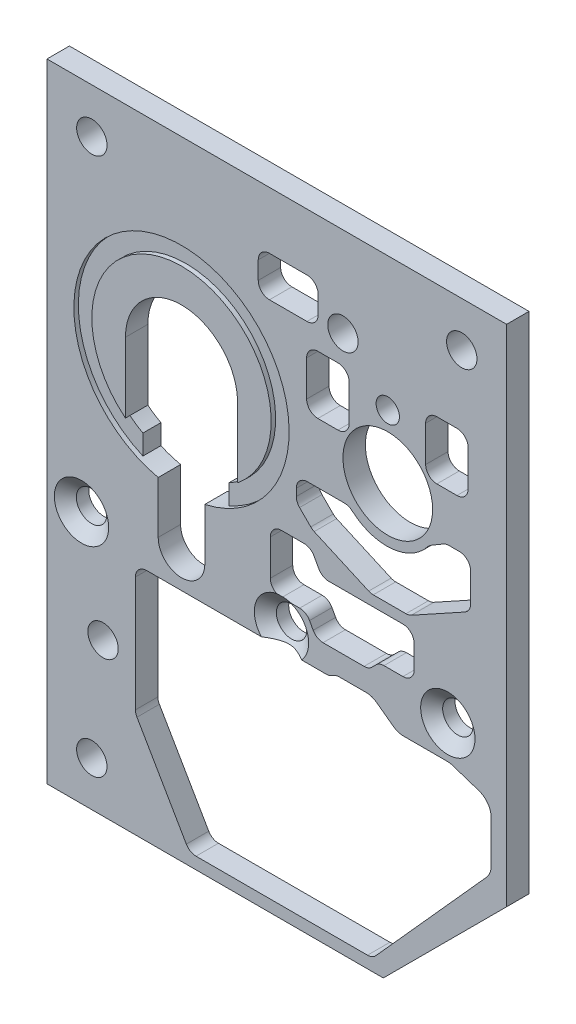
SolidWorks part; units mm, degrees
material "Acrylic (Medium-high impact)"
ref_plane "Front Plane" through (0, 0, 0) normal (0, 0, 1) x (1, 0, 0)
ref_plane "Top Plane" through (0, 0, 0) normal (0, 1, 0) x (1, 0, 0)
ref_plane "Right Plane" through (0, 0, 0) normal (1, 0, 0) x (0, 0, -1)
sketch "Sketch1" plane through (0, 0, 0) normal (0, 0, 1) x (1, 0, 0)
  line L5 (-65.0875, 0) -> (-65.0875, -88.9)
  line L6 (-65.0875, -88.9) -> (-17.4625, -88.9)
  line L7 (-17.4625, -88.9) -> (0, -71.4375)
  line L8 (0, -71.4375) -> (0, 0)
  line L9 (0, 0) -> (-65.0875, 0)
  line L10 (-65.0875, 0) -> (-65.0875, -88.9)
  line L11 (-65.0875, -88.9) -> (-17.4625, -88.9)
  line L12 (-17.4625, -88.9) -> (0, -71.4375)
  line L13 (0, -71.4375) -> (0, 0)
  line L14 (0, 0) -> (-65.0875, 0)
  dimension "D1" = 0
extrude "Boss-Extrude1" add sketch "Sketch1" against normal blind 3.175
hole_wizard "#6 Clearance Hole1" positions "Sketch3" profile "Sketch2" hole size "#6" standard "ANSI Inch" end condition through all
sketch "Sketch3" plane through (0, 0, 0) normal (0, 0, 1) x (1, 0, 0)
  point P0 (-58.7375, -6.35)
  point P3 (-6.35, -6.35)
  point P6 (-23.1775, -12.7)
  point P9 (-57.15, -67.31)
  point P12 (-58.7375, -82.55)
sketch "Sketch2" plane through (-58.7375, -6.35, 0) normal (1, 0, 0) x (0, -1, 0)
  line L0 (0, 0) -> (0, 3.175)
  line L1 (0, 3.175) -> (2.1526, 3.175)
  line L2 (2.1526, 3.175) -> (2.1526, 0)
  line L5 (2.1526, 0) -> (0, 0)
  line L11 (0, -6.35) -> (0, 107.95) construction
  dimension "Thru Hole Dia." = 4.3053
  dimension "Thru Hole Depth" = 3.175
sketch "Sketch4" plane through (0, 0, 0) normal (0, 0, 1) x (1, 0, 0)
  line L0 (-49.3395, -50.8) -> (-49.3395, -43.453) construction
  line L1 (-42.7355, -43.453) -> (-42.7355, -50.8) construction
  line L2 (-49.3395, -50.8) -> (-49.3395, -43.453)
  line L3 (-42.7355, -43.453) -> (-42.7355, -50.8)
  arc A0 (-42.7355, -43.453) -> (-49.3395, -43.453) centre (-46.0375, -28.575) ccw construction
  arc A1 (-49.3395, -50.8) -> (-42.7355, -50.8) centre (-46.0375, -50.8) ccw construction
  arc A2 (-42.7355, -43.453) -> (-49.3395, -43.453) centre (-46.0375, -28.575) ccw
  arc A3 (-49.3395, -50.8) -> (-42.7355, -50.8) centre (-46.0375, -50.8) ccw
extrude "Cut-Extrude1" cut sketch "Sketch4" against normal through all
sketch "Sketch5" plane through (0, 0, 0) normal (0, 0, 1) x (1, 0, 0)
  circle A0 centre (-16.8275, -27.94) radius 6.35
  circle A1 centre (-16.8275, -18.9484) radius 1.651
  dimension "D1" = 12.7
  dimension "D2" = 3.302
  dimension "D3" = 8.9916
extrude "Cut-Extrude2" cut sketch "Sketch5" against normal through all
hole_wizard "1/4 Clearance Hole1" positions "Sketch7" profile "Sketch6" hole size "1/4" standard "ANSI Inch" end condition through all
sketch "Sketch7" plane through (0, 0, 0) normal (0, 0, 1) x (1, 0, 0)
  point P0 (-9.2075, -65.0875)
sketch "Sketch6" plane through (-9.2075, -65.0875, 0) normal (1, 0, 0) x (0, -1, 0)
  line L0 (0, 0) -> (0, 3.175)
  line L1 (0, 3.175) -> (3.5712, 3.175)
  line L2 (3.5712, 3.175) -> (3.5712, 0)
  line L5 (3.5712, 0) -> (0, 0)
  line L11 (0, -6.35) -> (0, 107.95) construction
  dimension "Thru Hole Dia." = 7.1425
  dimension "Thru Hole Depth" = 3.175
sketch "Sketch8" plane through (0, 0, -3.175) normal (0, 0, -1) x (-1, 0, 0)
  line L0 (52.1335, -39.7163) -> (52.1335, -42.5427) construction
  line L1 (53.975, -28.575) -> (53.975, -38.4889) construction
  line L2 (38.1, -38.4889) -> (38.1, -28.575) construction
  line L3 (39.9415, -42.5427) -> (39.9415, -39.7163) construction
  line L4 (52.1335, -39.7163) -> (52.1335, -42.5427)
  line L5 (53.975, -28.575) -> (53.975, -38.4889)
  line L6 (38.1, -38.4889) -> (38.1, -28.575)
  line L7 (39.9415, -42.5427) -> (39.9415, -39.7163)
  arc A0 (52.1335, -39.7163) -> (53.975, -38.4889) centre (46.0375, -28.575) ccw construction
  arc A1 (53.975, -28.575) -> (38.1, -28.575) centre (46.0375, -28.575) ccw construction
  arc A2 (38.1, -38.4889) -> (39.9415, -39.7163) centre (46.0375, -28.575) ccw construction
  arc A3 (49.3395, -43.453) -> (42.7355, -43.453) centre (46.0375, -28.575) ccw construction
  arc A4 (52.1335, -39.7163) -> (53.975, -38.4889) centre (46.0375, -28.575) ccw
  arc A5 (53.975, -28.575) -> (38.1, -28.575) centre (46.0375, -28.575) ccw
  arc A6 (38.1, -38.4889) -> (39.9415, -39.7163) centre (46.0375, -28.575) ccw
  arc A7 (52.1335, -42.5427) -> (39.9415, -42.5427) centre (46.0375, -28.575) ccw
extrude "Boss-Extrude2" add sketch "Sketch8" against normal through all
sketch "Sketch9" plane through (0, 0, 0) normal (0, 0, 1) x (1, 0, 0)
  line L0 (-52.1335, -39.7163) -> (-52.1335, -42.5427) construction
  line L1 (-39.9415, -42.5427) -> (-39.9415, -39.7163) construction
  line L2 (-52.1335, -39.7163) -> (-52.1335, -42.5427)
  line L3 (-39.9415, -42.5427) -> (-39.9415, -39.7163)
  arc A0 (-42.7355, -43.453) -> (-49.3395, -43.453) centre (-46.0375, -28.575) ccw construction
  arc A1 (-53.975, -38.4889) -> (-52.1335, -39.7163) centre (-46.0375, -28.575) ccw construction
  arc A2 (-38.1, -38.4889) -> (-53.975, -38.4889) centre (-46.0375, -28.575) ccw construction
  arc A3 (-39.9415, -39.7163) -> (-38.1, -38.4889) centre (-46.0375, -28.575) ccw construction
  arc A4 (-39.9415, -42.5427) -> (-52.1335, -42.5427) centre (-46.0375, -28.575) ccw
  arc A5 (-53.975, -38.4889) -> (-52.1335, -39.7163) centre (-46.0375, -28.575) ccw
  arc A6 (-38.1, -38.4889) -> (-53.975, -38.4889) centre (-46.0375, -28.575) ccw
  arc A7 (-39.9415, -39.7163) -> (-38.1, -38.4889) centre (-46.0375, -28.575) ccw
extrude "Cut-Extrude3" cut sketch "Sketch9" against normal blind 0.635
hole_wizard "CSK for #6 Flat Head Machine Screw (100)1" positions "Sketch11" profile "Sketch10" countersink size "#6" standard "ANSI Inch" end condition through all
sketch "Sketch11" plane through (0, 0, 0) normal (0, 0, 1) x (1, 0, 0)
  point P1 (-31.877, -53.0919)
  point P5 (-60.198, -53.0919)
  point P8 (-8.321, -53.0919)
sketch "Sketch10" plane through (-31.877, -53.0919, 0) normal (1, 0, 0) x (0, -1, 0)
  line L0 (0, 0) -> (0, 3.175)
  line L1 (0, 3.175) -> (2.1526, 3.175)
  line L2 (2.1526, 3.175) -> (2.1526, 1.4209)
  line L3 (2.1526, 1.4209) -> (3.846, 0)
  line L5 (3.846, 0) -> (0, 0)
  line L6 (-2.1526, 1.4209) -> (-3.846, 0) construction
  line L11 (0, -6.35) -> (0, 107.95) construction
  dimension "Thru Hole Dia." = 4.3053
  dimension "Thru Hole Depth" = 3.175
  dimension "Near C'Sink Dia." = 7.692
  dimension "Near C'Sink Angle" = 100
sketch "Sketch13" plane through (0, 0, 0) normal (0, 0, 1) x (1, 0, 0)
  line L0 (-33.5834, -8.0877) -> (-28.2715, -8.0877)
  line L1 (-26.684, -9.6752) -> (-26.684, -12.1963)
  line L2 (-28.2715, -13.7838) -> (-33.5834, -13.7838)
  line L3 (-35.1709, -9.6752) -> (-35.1709, -12.1963)
  line L4 (-9.8743, -16.2715) -> (-7.0294, -16.2715)
  line L5 (-5.4419, -17.859) -> (-5.4419, -22.9231)
  line L6 (-7.0294, -24.5106) -> (-9.8743, -24.5106)
  line L7 (-11.4618, -22.9231) -> (-11.4618, -17.859)
  line L8 (-26.728, -16.6728) -> (-23.8831, -16.6728)
  line L9 (-22.2956, -18.2603) -> (-22.2956, -23.3243)
  line L10 (-23.8831, -24.9118) -> (-26.728, -24.9118)
  line L11 (-28.3155, -23.3243) -> (-28.3155, -18.2603)
  line L17 (-13.0908, -45.6924) -> (-13.0908, -48.9531)
  line L23 (-33.4611, -47.8684) -> (-33.4611, -42.8044)
  line L24 (-29.3162, -37.1302) -> (-27.7292, -38.7172)
  line L25 (-27.2516, -39.0452) -> (-19.5276, -42.4798)
  line L26 (-18.8826, -42.6167) -> (-14.2496, -42.6167)
  line L27 (-13.4825, -42.4191) -> (-5.915, -38.243)
  line L28 (-5.0945, -36.8531) -> (-5.0945, -32.7951)
  line L29 (-6.682, -31.2076) -> (-8.167, -31.2076)
  line L32 (-22.9356, -33.4058) -> (-28.1937, -33.4058)
  line L33 (-29.7812, -34.9933) -> (-29.7812, -36.0077)
  line L34 (-50.973, -55.6802) -> (-25.5623, -55.6802)
  line L40 (-19.6965, -87.2192) -> (-43.9811, -87.2192)
  line L41 (-45.3548, -86.4273) -> (-52.3467, -74.3556)
  line L42 (-52.5605, -73.56) -> (-52.5605, -57.2677)
  line L43 (-14.6783, -44.1049) -> (-25.206, -44.1049)
  line L44 (-26.5981, -43.2804) -> (-27.2773, -42.0413)
  line L45 (-28.6694, -41.2169) -> (-31.8736, -41.2169)
  line L48 (-25.9975, -52.0435) -> (-20.1851, -52.0435)
  line L49 (-19.0626, -51.5785) -> (-18.4896, -51.0056)
  line L50 (-17.3671, -50.5406) -> (-14.6783, -50.5406)
  line L51 (-27.3896, -51.219) -> (-27.9041, -50.2804)
  line L52 (-29.2962, -49.4559) -> (-31.8736, -49.4559)
  line L54 (-24.662, -55.4002) -> (-24.6221, -55.3728)
  line L58 (-8.9781, -31.4305) -> (-10.7271, -32.4701)
  line L61 (-2.1881, -67.5296) -> (-2.1881, -61.5652)
  line L62 (-3.9295, -59.154) -> (-7.632, -57.9277)
  line L63 (-8.4306, -57.7989) -> (-14.5582, -57.7989)
  line L64 (-16.0658, -57.303) -> (-18.3903, -55.5886)
  line L65 (-19.898, -55.0928) -> (-23.7218, -55.0928)
  line L66 (-2.8379, -69.2263) -> (-18.4811, -86.653)
  arc A0 (-28.2715, -8.0877) -> (-26.684, -9.6752) centre (-28.2715, -9.6752) cw
  arc A1 (-26.684, -12.1963) -> (-28.2715, -13.7838) centre (-28.2715, -12.1963) cw
  arc A2 (-33.5834, -13.7838) -> (-35.1709, -12.1963) centre (-33.5834, -12.1963) cw
  arc A3 (-33.5834, -8.0877) -> (-35.1709, -9.6752) centre (-33.5834, -9.6752) ccw
  arc A4 (-5.4419, -22.9231) -> (-7.0294, -24.5106) centre (-7.0294, -22.9231) cw
  arc A5 (-9.8743, -24.5106) -> (-11.4618, -22.9231) centre (-9.8743, -22.9231) cw
  arc A6 (-9.8743, -16.2715) -> (-11.4618, -17.859) centre (-9.8743, -17.859) ccw
  arc A7 (-7.0294, -16.2715) -> (-5.4419, -17.859) centre (-7.0294, -17.859) cw
  arc A8 (-22.2956, -23.3243) -> (-23.8831, -24.9118) centre (-23.8831, -23.3243) cw
  arc A9 (-26.728, -24.9118) -> (-28.3155, -23.3243) centre (-26.728, -23.3243) cw
  arc A10 (-26.728, -16.6728) -> (-28.3155, -18.2603) centre (-26.728, -18.2603) ccw
  arc A11 (-23.8831, -16.6728) -> (-22.2956, -18.2603) centre (-23.8831, -18.2603) cw
  arc A16 (-13.0908, -48.9531) -> (-14.6783, -50.5406) centre (-14.6783, -48.9531) cw
  arc A19 (-14.6783, -44.1049) -> (-13.0908, -45.6924) centre (-14.6783, -45.6924) cw
  arc A21 (-31.8736, -49.4559) -> (-33.4611, -47.8684) centre (-31.8736, -47.8684) cw
  arc A22 (-31.8736, -41.2169) -> (-33.4611, -42.8044) centre (-31.8736, -42.8044) ccw
  arc A24 (-19.5276, -42.4798) -> (-18.8826, -42.6167) centre (-18.8826, -41.0292) ccw
  arc A25 (-14.2496, -42.6167) -> (-13.4825, -42.4191) centre (-14.2496, -41.0292) ccw
  arc A26 (-5.915, -38.243) -> (-5.0945, -36.8531) centre (-6.682, -36.8531) ccw
  arc A27 (-5.0945, -32.7951) -> (-6.682, -31.2076) centre (-6.682, -32.7951) ccw
  arc A31 (-27.7292, -38.7172) -> (-27.2516, -39.0452) centre (-26.6066, -37.5947) ccw
  arc A32 (-29.3162, -37.1302) -> (-29.7812, -36.0077) centre (-28.1937, -36.0077) cw
  arc A33 (-28.1937, -33.4058) -> (-29.7812, -34.9933) centre (-28.1937, -34.9933) ccw
  arc A39 (-18.4811, -86.653) -> (-19.6965, -87.2192) centre (-19.6965, -85.6317) cw
  arc A40 (-43.9811, -87.2192) -> (-45.3548, -86.4273) centre (-43.9811, -85.6317) cw
  arc A41 (-52.3467, -74.3556) -> (-52.5605, -73.56) centre (-50.973, -73.56) cw
  arc A42 (-50.973, -55.6802) -> (-52.5605, -57.2677) centre (-50.973, -57.2677) ccw
  arc A43 (-27.2773, -42.0413) -> (-28.6694, -41.2169) centre (-28.6694, -42.8044) ccw
  arc A44 (-25.206, -44.1049) -> (-26.5981, -43.2804) centre (-25.206, -42.5174) cw
  arc A45 (-18.4896, -51.0056) -> (-17.3671, -50.5406) centre (-17.3671, -52.1281) cw
  arc A46 (-20.1851, -52.0435) -> (-19.0626, -51.5785) centre (-20.1851, -50.456) ccw
  arc A47 (-27.3896, -51.219) -> (-25.9975, -52.0435) centre (-25.9975, -50.456) ccw
  arc A48 (-27.9041, -50.2804) -> (-29.2962, -49.4559) centre (-29.2962, -51.0434) ccw
  arc A51 (-24.6221, -55.3728) -> (-23.7218, -55.0928) centre (-23.7218, -56.6803) cw
  arc A52 (-24.662, -55.4002) -> (-25.5623, -55.6802) centre (-25.5623, -54.0927) cw
  arc A53 (-11.1669, -32.8573) -> (-21.8769, -33.8104) centre (-16.9676, -28.3255) cw
  arc A54 (-22.9356, -33.4058) -> (-21.8769, -33.8104) centre (-22.9356, -34.9933) cw
  arc A55 (-11.1669, -32.8573) -> (-10.7271, -32.4701) centre (-9.916, -33.8347) cw
  arc A56 (-8.167, -31.2076) -> (-8.9781, -31.4305) centre (-8.167, -32.7951) ccw
  arc A59 (-18.3903, -55.5886) -> (-19.898, -55.0928) centre (-19.898, -57.6328) ccw
  arc A60 (-14.5582, -57.7989) -> (-16.0658, -57.303) centre (-14.5582, -55.2589) cw
  arc A61 (-7.632, -57.9277) -> (-8.4306, -57.7989) centre (-8.4306, -60.3389) ccw
  arc A62 (-2.8379, -69.2263) -> (-2.1881, -67.5296) centre (-4.7281, -67.5296) ccw
  arc A64 (-2.1881, -61.5652) -> (-3.9295, -59.154) centre (-4.7281, -61.5652) ccw
  dimension "D1" = 1.5875
  dimension "D2" = 1.5875
  dimension "D3" = 1.5875
  dimension "D4" = 1.5875
  dimension "D6" = 1.5875
  dimension "D7" = 1.5875
  dimension "D8" = 1.5875
extrude "Backlighting Holes" cut sketch "Sketch13" against normal through all
